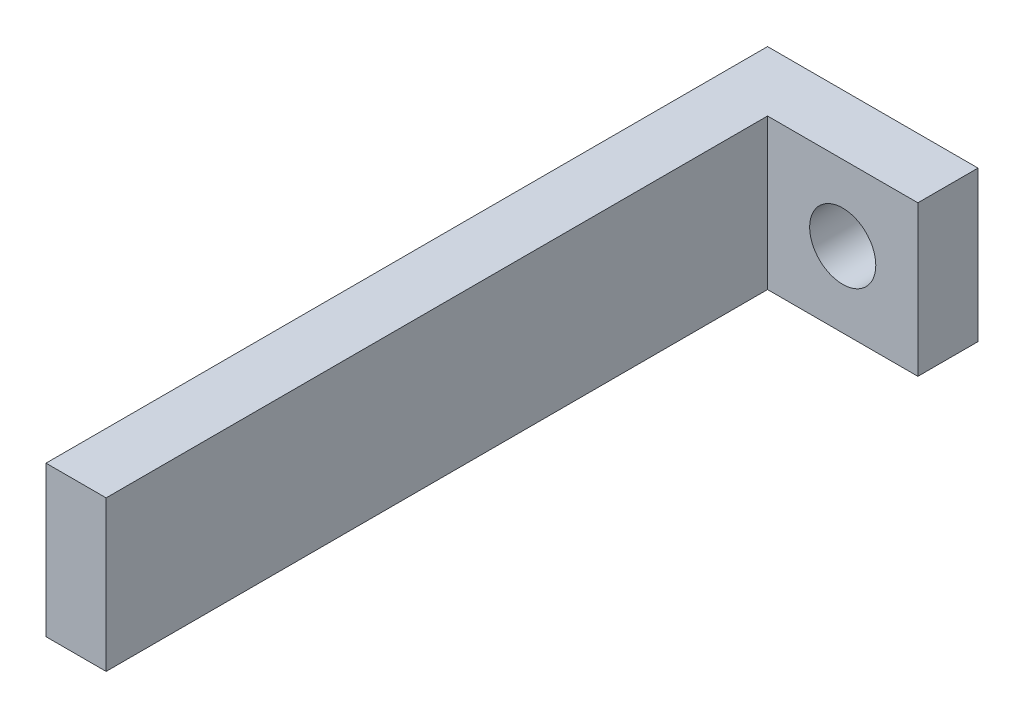
SolidWorks part; units mm, degrees
ref_plane "正面" through (0, 0, 0) normal (0, 0, 1) x (1, 0, 0)
ref_plane "平面" through (0, 0, 0) normal (0, 1, 0) x (1, 0, 0)
ref_plane "右側面" through (0, 0, 0) normal (1, 0, 0) x (0, 0, -1)
sketch "ｽｹｯﾁ1" plane through (0, 0, 0) normal (0, 0, 1) x (1, 0, 0)
  line L1 (-38.8056, 35.4193) -> (-13.8056, 35.4193)
  line L2 (-38.8056, 35.4193) -> (-38.8056, 10.4193)
  line L3 (-38.8056, 10.4193) -> (-13.8056, 10.4193)
  line L4 (-13.8056, 35.4193) -> (-13.8056, 10.4193)
  line L5 (-38.8056, 35.4193) -> (-13.8056, 10.4193) construction
  line L6 (-38.8056, 10.4193) -> (-13.8056, 35.4193) construction
  point P0 (-26.3056, 22.9193)
  dimension "D1" = 25
  dimension "D2" = 25
extrude "ﾎﾞｽ - 押し出し1" add sketch "ｽｹｯﾁ1" along normal blind 10
sketch "ｽｹｯﾁ2" plane through (0, 0, 0) normal (0, 0, -1) x (-1, 0, 0)
  line L0 (38.8056, 35.4193) -> (38.8056, 10.4193)
  line L1 (38.8056, 35.4193) -> (48.8056, 35.4193)
  line L2 (38.8056, 10.4193) -> (48.8056, 10.4193)
  line L3 (48.8056, 35.4193) -> (48.8056, 10.4193)
  dimension "D1" = 25
  dimension "D2" = 10
extrude "ﾎﾞｽ - 押し出し2" add sketch "ｽｹｯﾁ2" against normal blind 120
sketch "ｽｹｯﾁ3" plane through (0, 0, 120) normal (0, 0, 1) x (1, 0, 0)
  line L0 (-38.8056, 35.4193) -> (-38.8056, 10.4193)
  line L1 (-38.8056, 35.4193) -> (-13.8056, 35.4193)
  line L2 (-38.8056, 10.4193) -> (-13.8056, 10.4193)
  line L3 (-13.8056, 35.4193) -> (-13.8056, 10.4193)
  dimension "D1" = 25
  dimension "D2" = 25
sketch "ｽｹｯﾁ6" plane through (0, 0, 0) normal (0, 0, -1) x (-1, 0, 0)
  line L0 (48.8056, 10.4193) -> (13.8056, 10.4193) construction
  line L1 (13.8056, 10.4193) -> (13.8056, 35.4193) construction
  circle A0 centre (26.3056, 22.9193) radius 5.5
  dimension "D1" = 12.5
  dimension "D2" = 12.5
extrude "ｶｯﾄ - 押し出し1" cut sketch "ｽｹｯﾁ6" against normal through all
